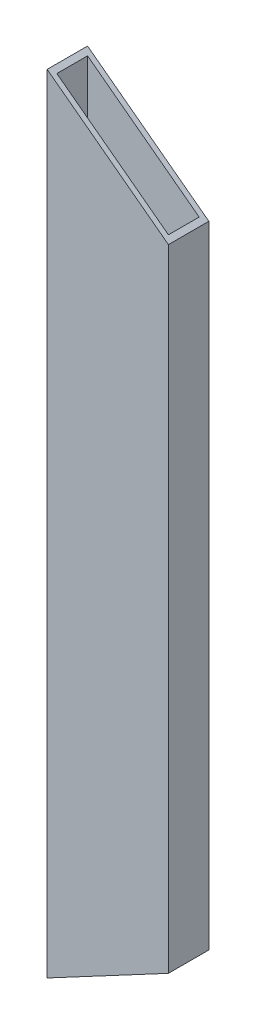
SolidWorks part; units mm, degrees
note: '?' marks a value the reader was unsure of.
material "A500"
ref_plane "Front Plane" through (0, 0, 0) normal (0, 0, 1) x (1, 0, 0)
ref_plane "Top Plane" through (0, 0, 0) normal (0, 1, 0) x (1, 0, 0)
ref_plane "Right Plane" through (0, 0, 0) normal (1, 0, 0) x (0, 0, -1)
sketch "Sketch1" plane through (0, 0, 0) normal (0, 1, 0) x (1, 0, 0)
  line L0 (0, 9.652) -> (0, 12.7) construction
  line L1 (-38.1, 12.7) -> (38.1, 12.7)
  line L2 (-38.1, 12.7) -> (-38.1, -12.7)
  line L3 (-38.1, -12.7) -> (38.1, -12.7)
  line L4 (38.1, 12.7) -> (38.1, -12.7)
  line L5 (-35.052, 9.652) -> (35.052, 9.652)
  line L6 (-35.052, 9.652) -> (-35.052, -9.652)
  line L7 (-35.052, -9.652) -> (35.052, -9.652)
  line L8 (35.052, 9.652) -> (35.052, -9.652)
  line L9 (35.052, 0) -> (38.1, 0) construction
  line L10 (0, -9.652) -> (0, -12.7) construction
  line L11 (-35.052, 0) -> (-38.1, 0) construction
  line L12 (0, 9.652) -> (0, 0) construction
  line L13 (0, 0) -> (-35.052, 0) construction
  dimension "D1" = 76.2
  dimension "D2" = 25.4
  dimension "D3" = 3.048
extrude "Boss-Extrude1" add sketch "Sketch1" along normal up to vertex (536.3412 mm away)
ref_plane "Plane1" through (0, 0, 0) normal (0, 0, 1) x (1, 0, 0)
sketch "Sketch2" plane through (0, 0, 0) normal (0, 0, 1) x (1, 0, 0)
  line L0 (0, 0) -> (0, 536.3412) construction
  line L1 (-38.1, 536.3412) -> (38.1, 536.3412) construction
  line L2 (0, 268.1706) -> (-38.1, 268.1706) construction
  line L3 (-38.1, 536.3412) -> (-38.1, 0) construction
  line L4 (0, 268.1706) -> (38.1, 268.1706) construction
  line L5 (38.1, 536.3412) -> (38.1, 0) construction
ref_axis "Axis1" through (0, 536.3412, 0) along (0, -1, 0)?
ref_plane "Plane2" through (0, 536.3412, 0) normal (0.7994, -0.6009, 0) x (0, 0, -1)
sketch "Sketch3" plane through (0, 536.3412, 0) normal (0.7994, -0.6009, 0) x (0, 0, -1)
  line L1 (12.7, -38.1) -> (-12.7, -38.1) construction
  line L3 (-12.7, 38.1) -> (12.7, 38.1) construction
  line L4 (12.7, 38.1) -> (12.7, -38.1)
  line L5 (12.7, -38.1) -> (-12.7, -38.1)
  line L6 (-12.7, -38.1) -> (-12.7, 38.1)
  line L7 (-12.7, 38.1) -> (12.7, 38.1)
extrude "Cut-Extrude1" cut sketch "Sketch3" against normal up to vertex and the other way up to vertex
ref_plane "Plane3" through (0, 0, 0) normal (0.8824, 0.4705, 0) x (0, 0, -1)
sketch "Sketch4" plane through (0, 0, 0) normal (0.8824, 0.4705, 0) x (0, 0, -1)
  line L0 (-12.7, -38.1) -> (12.7, -38.1) construction
  line L1 (12.7, -38.1) -> (12.7, 38.1) construction
  line L2 (-12.7, 38.1) -> (-12.7, -38.1) construction
  line L3 (-12.7, -38.1) -> (12.7, -38.1)
  line L4 (12.7, -38.1) -> (12.7, 38.1)
  line L5 (-12.7, 38.1) -> (-12.7, -38.1)
  line L6 (-12.7, 38.1) -> (12.7, 38.1)
extrude "Cut-Extrude2" cut sketch "Sketch4" against normal up to vertex and the other way up to vertex
equation "\"tubeMainWidth\"= 76.2mm"
equation "\"tubeSecondWidth\"= 25.4mm"
equation "\"tubeThickness\"= 3.048mm"
equation "\"halfMainWidthOfTubing\"= (\"tubeMainWidth\"/2)"
equation "\"D1@Sketch1\"=\"tubeMainWidth\""
equation "\"D2@Sketch1\"=\"tubeSecondWidth\""
equation "\"D3@Sketch1\"=\"tubeThickness\""
equation "\"D2@Cut-Extrude1\"=\"halfMainWidthOfTubing\""
